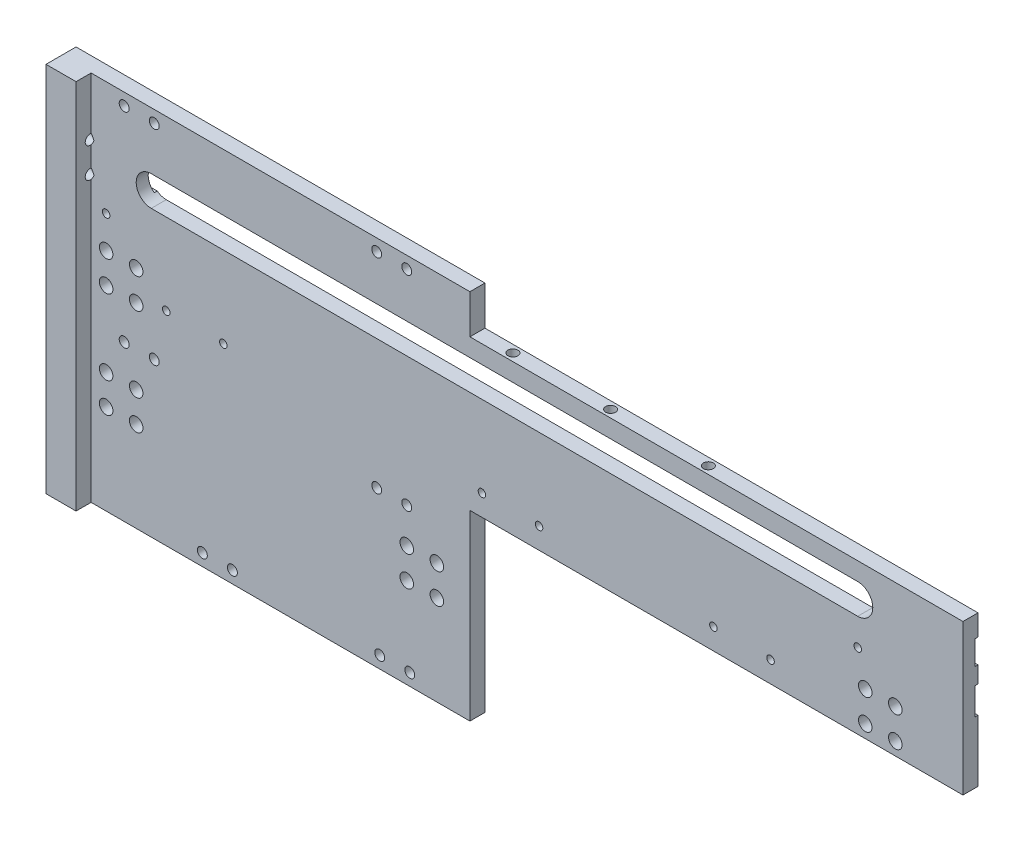
SolidWorks part; units mm, degrees
ref_plane "前视基准面" through (0, 0, 0) normal (0, 0, 1) x (1, 0, 0)
ref_plane "上视基准面" through (0, 0, 0) normal (0, 1, 0) x (1, 0, 0)
ref_plane "右视基准面" through (0, 0, 0) normal (1, 0, 0) x (0, 0, -1)
sketch "草图4" plane through (0, 0, 0) normal (0, 0, 1) x (1, 0, 0)
  line L0 (30, 99.7) -> (265, 99.7) construction
  line L1 (0, 0) -> (136, 0)
  line L2 (0, 0) -> (0, 123.7)
  line L3 (0, 123.7) -> (136, 123.7)
  line L4 (300, 60.7) -> (300, 110.7)
  line L5 (30, 104.7) -> (265, 104.7)
  line L6 (136, 123.7) -> (136, 110.7)
  line L7 (136, 110.7) -> (300, 110.7)
  line L9 (30, 94.7) -> (265, 94.7)
  line L10 (136, 0) -> (136, 60.7)
  line L11 (136, 60.7) -> (300, 60.7)
  arc A0 (30, 104.7) -> (30, 94.7) centre (30, 99.7) ccw
  arc A1 (265, 94.7) -> (265, 104.7) centre (265, 99.7) ccw
  dimension "D1" = 300
  dimension "D2" = 136
  dimension "D3" = 13
  dimension "D4" = 63
  dimension "D5" = 123.7
  dimension "D6" = 10
  dimension "D7" = 30
  dimension "D8" = 265
  dimension "D9" = 24
extrude "凸台-拉伸1" add sketch "草图4" along normal blind 10
sketch "草图5" plane through (300, 0, 0) normal (1, 0, 0) x (0, 0, -1)
  line L1 (0, 60.7) -> (0, 110.7) construction
  line L2 (-10, 123.7) -> (0, 123.7) construction
  line L3 (0, 103.7) -> (-1, 103.7)
  line L4 (0, 103.7) -> (0, 95.7)
  line L6 (0, 95.7) -> (-1, 95.7)
  line L7 (0, 90.2) -> (-1, 90.2)
  line L8 (0, 90.2) -> (0, 81.2)
  line L9 (0, 81.2) -> (-1, 81.2)
  line L10 (-1, 90.2) -> (-1, 81.2)
  line L12 (-1, 103.7) -> (-1, 95.7)
  dimension "D1" = 20
  dimension "D2" = 8
  dimension "D3" = 33.5
  dimension "D4" = 9
  dimension "D5" = 1
extrude "切除-拉伸1" cut sketch "草图5" against normal through all
hole_wizard "M4 螺纹孔1" positions "草图6" profile "草图7" tap size "M4" standard "ISO"
sketch "草图6" plane through (0, 0, 0) normal (-1, 0, 0) x (0, 0, 1)
  line L0 (10, 123.7) -> (10, 0) construction
  line L1 (10, 123.7) -> (0, 123.7) construction
  point P0 (5.304, 104.7)
  point P2 (5.304, 94.7)
  dimension "D1" = 4.696
  dimension "D2" = 19
  dimension "D3" = 29
sketch "草图7" plane through (0, 104.7, 5.304) normal (0, 1, 0) x (0, 0, 1)
  line L0 (0, 0) -> (0, 11.0914)
  line L1 (0, 11.0914) -> (1.65, 10.1)
  line L2 (1.65, 10.1) -> (1.65, 0)
  line L5 (1.65, 0) -> (0, 0)
  line L10 (0, 11.0914) -> (-1.65, 10.1) construction
  line L11 (0, -6.35) -> (0, 107.95) construction
  dimension "螺纹孔钻头直径" = 3.3
  dimension "螺纹孔钻头深度" = 10.1
  dimension "导头角度" = 118
cosmetic thread "孔螺蚊线1" parameters "D1"=8, "D2"=4
cosmetic thread "孔螺蚊线2" parameters "D1"=8, "D2"=4
sketch "草图8" plane through (0, 0, 10) normal (0, 0, 1) x (1, 0, 0)
  line L1 (136, 123.7) -> (0, 123.7) construction
  line L2 (10, 123.7) -> (316.5249, 123.7)
  line L3 (10, 123.7) -> (10, -39.0626)
  line L4 (10, -39.0626) -> (316.5249, -39.0626)
  line L5 (316.5249, 123.7) -> (316.5249, -39.0626)
  line L6 (0, 123.7) -> (0, 0) construction
  dimension "D1" = 10
extrude "切除-拉伸2" cut sketch "草图8" against normal blind 5
hole_wizard "M4 螺纹孔2" positions "草图9" profile "草图10" tap size "M4" standard "ISO"
sketch "草图9" plane through (0, 0, 5) normal (0, 0, 1) x (1, 0, 0)
  line L0 (136, 123.7) -> (10, 123.7) construction
  line L1 (0, 123.7) -> (0, 0) construction
  point P0 (21, 119.7)
  point P2 (31, 119.7)
  point P4 (105, 119.7)
  point P6 (115, 119.7)
  point P8 (21, 51.7)
  point P10 (31, 51.7)
  point P12 (105, 51.7)
  point P14 (115, 51.7)
  point P16 (47, 4)
  point P18 (57, 4)
  point P20 (106, 4)
  point P22 (116, 4)
  dimension "D1" = 4
  dimension "D2" = 72
  dimension "D3" = 119.7
  dimension "D4" = 21
  dimension "D5" = 31
  dimension "D6" = 105
  dimension "D7" = 115
  dimension "D8" = 47
  dimension "D9" = 57
  dimension "D10" = 106
  dimension "D11" = 116
sketch "草图10" plane through (21, 119.7, 5) normal (1, 0, 0) x (0, -1, 0)
  line L0 (0, 0) -> (0, 11.0914)
  line L1 (0, 11.0914) -> (1.65, 10.1)
  line L2 (1.65, 10.1) -> (1.65, 0)
  line L5 (1.65, 0) -> (0, 0)
  line L10 (0, 11.0914) -> (-1.65, 10.1) construction
  line L11 (0, -6.35) -> (0, 107.95) construction
  dimension "螺纹孔钻头直径" = 3.3
  dimension "螺纹孔钻头深度" = 10.1
  dimension "导头角度" = 118
cosmetic thread "孔螺蚊线3" parameters "D1"=5, "D2"=4
cosmetic thread "孔螺蚊线4" parameters "D1"=5, "D2"=4
cosmetic thread "孔螺蚊线5" parameters "D1"=5, "D2"=4
cosmetic thread "孔螺蚊线6" parameters "D1"=5, "D2"=4
cosmetic thread "孔螺蚊线7" parameters "D1"=5, "D2"=4
cosmetic thread "孔螺蚊线8" parameters "D1"=5, "D2"=4
cosmetic thread "孔螺蚊线9" parameters "D1"=5, "D2"=4
cosmetic thread "孔螺蚊线10" parameters "D1"=5, "D2"=4
cosmetic thread "孔螺蚊线11" parameters "D1"=5, "D2"=4
cosmetic thread "孔螺蚊线12" parameters "D1"=5, "D2"=4
cosmetic thread "孔螺蚊线13" parameters "D1"=5, "D2"=4
cosmetic thread "孔螺蚊线14" parameters "D1"=5, "D2"=4
hole_wizard "M3 螺纹孔1" positions "草图11" profile "草图12" tap size "M3" standard "ISO"
sketch "草图11" plane through (0, 0, 5) normal (0, 0, 1) x (1, 0, 0)
  line L0 (0, 123.7) -> (0, 0) construction
  line L1 (10, 123.7) -> (0, 123.7) construction
  point P0 (15, 85.7)
  point P2 (265, 85.7)
  dimension "D1" = 15
  dimension "D2" = 265
  dimension "D3" = 38
sketch "草图12" plane through (15, 85.7, 5) normal (1, 0, 0) x (0, -1, 0)
  line L0 (0, 0) -> (0, 8.2511)
  line L1 (0, 8.2511) -> (1.25, 7.5)
  line L2 (1.25, 7.5) -> (1.25, 0)
  line L5 (1.25, 0) -> (0, 0)
  line L10 (0, 8.2511) -> (-1.25, 7.5) construction
  line L11 (0, -6.35) -> (0, 107.95) construction
  dimension "螺纹孔钻头直径" = 2.5
  dimension "螺纹孔钻头深度" = 7.5
  dimension "导头角度" = 118
cosmetic thread "孔螺蚊线15" parameters "D1"=4, "D2"=3
cosmetic thread "孔螺蚊线16" parameters "D1"=4, "D2"=3
hole_wizard "M3 螺纹孔2" positions "草图13" profile "草图14" tap size "M3" standard "ISO"
sketch "草图13" plane through (0, 0, 5) normal (0, 0, 1) x (1, 0, 0)
  line L0 (136, 123.7) -> (10, 123.7) construction
  line L1 (0, 123.7) -> (0, 0) construction
  point P0 (35, 67.7)
  point P2 (54, 67.7)
  point P4 (140, 67.7)
  point P6 (159, 67.7)
  point P8 (217, 67.7)
  point P10 (236, 67.7)
  dimension "D1" = 56
  dimension "D2" = 35
  dimension "D3" = 54
  dimension "D4" = 140
  dimension "D5" = 159
  dimension "D6" = 217
  dimension "D7" = 236
sketch "草图14" plane through (35, 67.7, 5) normal (1, 0, 0) x (0, -1, 0)
  line L0 (0, 0) -> (0, 8.2511)
  line L1 (0, 8.2511) -> (1.25, 7.5)
  line L2 (1.25, 7.5) -> (1.25, 0)
  line L5 (1.25, 0) -> (0, 0)
  line L10 (0, 8.2511) -> (-1.25, 7.5) construction
  line L11 (0, -6.35) -> (0, 107.95) construction
  dimension "螺纹孔钻头直径" = 2.5
  dimension "螺纹孔钻头深度" = 7.5
  dimension "导头角度" = 118
cosmetic thread "孔螺蚊线17" parameters "D1"=5, "D2"=3
cosmetic thread "孔螺蚊线18" parameters "D1"=5, "D2"=3
cosmetic thread "孔螺蚊线19" parameters "D1"=5, "D2"=3
cosmetic thread "孔螺蚊线20" parameters "D1"=5, "D2"=3
cosmetic thread "孔螺蚊线21" parameters "D1"=5, "D2"=3
cosmetic thread "孔螺蚊线22" parameters "D1"=5, "D2"=3
sketch "草图15" plane through (0, 0, 5) normal (0, 0, 1) x (1, 0, 0)
  line L0 (0, 123.7) -> (0, 0) construction
  line L1 (136, 123.7) -> (10, 123.7) construction
  line L2 (20, 75) -> (20, 133.6461) construction
  line L3 (4.9076, 70) -> (26.7652, 70) construction
  circle A0 centre (15, 75) radius 2.25
  circle A1 centre (25, 75) radius 2.25
  circle A2 centre (25, 65) radius 2.25
  circle A3 centre (15, 65) radius 2.25
  dimension "D1" = 4.5
  dimension "D2" = 15
  dimension "D3" = 48.7
  dimension "D4" = 5
  dimension "D5" = 5
extrude "切除-拉伸3" cut sketch "草图15" against normal blind 5
pattern_linear "阵列(线性)1" count 2 spacing 252.5 along (1, 0, 0) of "切除-拉伸3"
pattern_linear "阵列(线性)2" count 2 spacing 35 along (0, -1, 0) of "切除-拉伸3"
pattern_linear "阵列(线性)3" count 2 spacing 100 along (1, 0, 0) of "阵列(线性)2"
sketch "草图16" plane through (0, 0, 5) normal (0, 0, 1) x (1, 0, 0)
  line L1 (105.3882, 81.0569) -> (130.1902, 81.0569)
  line L2 (105.3882, 81.0569) -> (105.3882, 58.9705)
  line L3 (105.3882, 58.9705) -> (130.1902, 58.9705)
  line L4 (130.1902, 81.0569) -> (130.1902, 58.9705)
extrude "凸台-拉伸2" add sketch "草图16" against normal up to surface (5 mm away) up to face at (122.75, 75, 0)
hole_wizard "M4 螺纹孔3" positions "草图17" profile "草图18" tap size "M4" standard "ISO"
sketch "草图17" plane through (0, 60.7, 0) normal (0, -1, 0) x (-1, 0, 0)
  line L0 (-136, -5) -> (-300, -5) construction
  line L1 (0, -10) -> (0, 0) construction
  point P0 (-147.8, -2.5)
  point P2 (-180.3, -2.5)
  point P4 (-212.8, -2.5)
  dimension "D1" = 2.5
  dimension "D2" = 147.8
  dimension "D3" = 180.3
  dimension "D4" = 212.8
sketch "草图18" plane through (147.8, 60.7, 2.5) normal (1, 0, 0) x (0, 0, -1)
  line L0 (0, 0) -> (0, 11.0914)
  line L1 (0, 11.0914) -> (1.65, 10.1)
  line L2 (1.65, 10.1) -> (1.65, 0)
  line L5 (1.65, 0) -> (0, 0)
  line L10 (0, 11.0914) -> (-1.65, 10.1) construction
  line L11 (0, -6.35) -> (0, 107.95) construction
  dimension "螺纹孔钻头直径" = 3.3
  dimension "螺纹孔钻头深度" = 10.1
  dimension "导头角度" = 118
cosmetic thread "孔螺蚊线23" parameters "D1"=8, "D2"=4
cosmetic thread "孔螺蚊线24" parameters "D1"=8, "D2"=4
cosmetic thread "孔螺蚊线25" parameters "D1"=8, "D2"=4
ref_plane "基准面1" through (0, 85.7, 0) normal (0, -1, 0) x (-1, 0, 0)
mirror "镜向1" about plane through (0, 85.7, 0) normal (0, -1, 0) of "M4 螺纹孔3"
